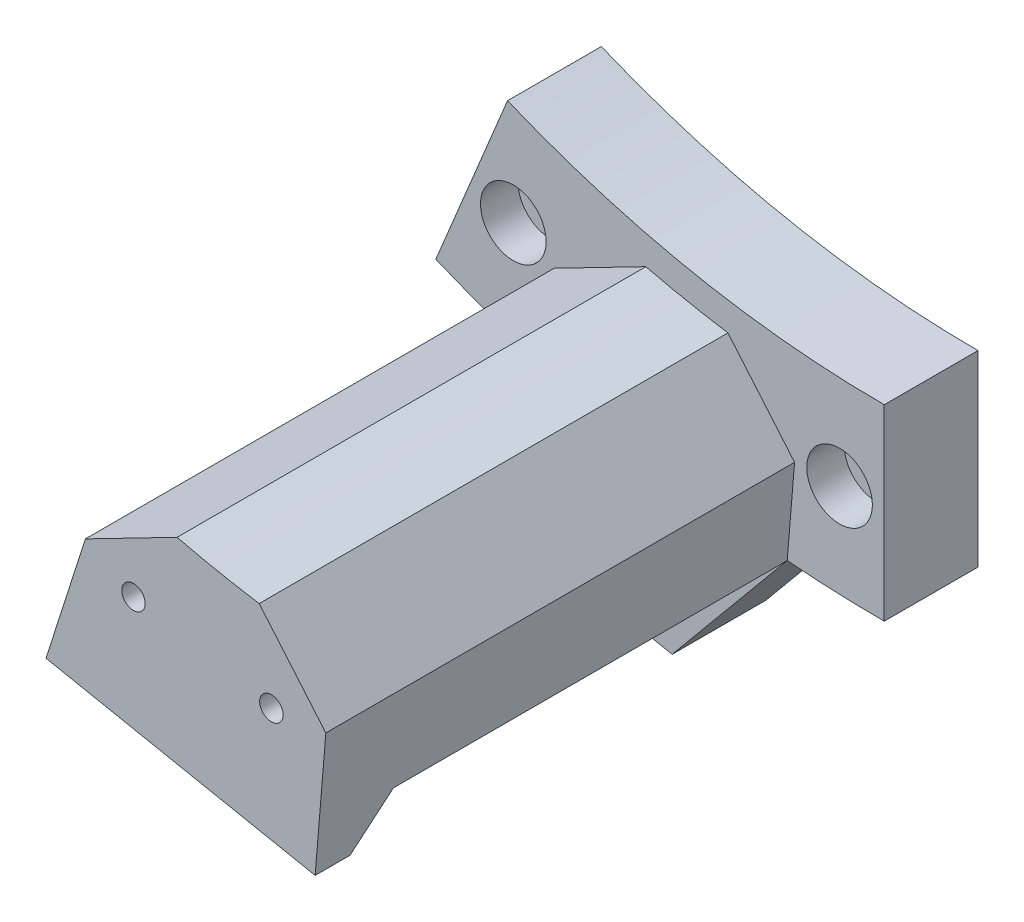
SolidWorks part; units mm, degrees
ref_plane "Plan de face" through (0, 0, 0) normal (0, 0, 1) x (1, 0, 0)
ref_plane "Plan de dessus" through (0, 0, 0) normal (0, 1, 0) x (1, 0, 0)
ref_plane "Plan de droite" through (0, 0, 0) normal (1, 0, 0) x (0, 0, -1)
sketch "Esquisse1" plane through (0, 0, 0) normal (0, 0, 1) x (1, 0, 0)
  line L0 (0, 0) -> (0, -125) construction
  line L1 (0, 0) -> (-47.8354, -115.4849) construction
  line L2 (-40.1818, -97.0074) -> (-47.8354, -115.4849)
  line L3 (0, -105) -> (0, -125)
  arc A0 (0, -125) -> (-47.8354, -115.4849) centre (0, 0) cw
  arc A1 (0, -105) -> (-40.1818, -97.0074) centre (0, 0) cw
  dimension "D2" = 125
  dimension "D3" = 105
  dimension "D1" = 22.5
extrude "Boss.-Extru.1" add sketch "Esquisse1" along normal blind 10
sketch "Esquisse2" plane through (0, 0, 10) normal (0, 0, 1) x (1, 0, 0)
  line L0 (0, 0) -> (-24.3863, -122.5982) construction
  line L1 (0, 0) -> (-10.351, -124.5707) construction
  line L2 (0, 0) -> (-38.108, -119.0495) construction
  line L3 (-32.9253, -102.8587) -> (-38.108, -119.0495)
  line L4 (-8.9433, -107.6291) -> (-10.351, -124.5707)
  arc A0 (-47.8354, -115.4849) -> (0, -125) centre (0, 0) ccw construction
  arc A1 (-10.351, -124.5707) -> (-38.108, -119.0495) centre (0, 0) cw
  arc A2 (-8.9433, -107.6291) -> (-32.9253, -102.8587) centre (0, 0) cw
  arc A3 (-40.1818, -97.0074) -> (0, -105) centre (0, 0) ccw construction
  point P10 (-24.3863, -122.5982)
  dimension "D1" = 3
  dimension "D2" = 13
extrude "Boss.-Extru.2" add sketch "Esquisse2" along normal blind 48
sketch "Esquisse4" plane through (0, 0, 58) normal (0, 0, 1) x (1, 0, 0)
  line L0 (-39.4132, -123.1267) -> (-10.7055, -128.837)
  line L1 (-10.7055, -128.837) -> (-8.9433, -107.6291)
  line L2 (-32.9253, -102.8587) -> (-39.4132, -123.1267)
  line L3 (-32.9253, -102.8587) -> (-38.108, -119.0495) construction
  line L4 (-10.351, -124.5707) -> (-8.9433, -107.6291) construction
  arc A0 (-32.9253, -102.8587) -> (-8.9433, -107.6291) centre (0, 0) ccw construction
  arc A1 (-32.9253, -102.8587) -> (-8.9433, -107.6291) centre (0, 0) ccw
  arc A2 (-38.108, -119.0495) -> (-10.351, -124.5707) centre (0, 0) ccw construction
  point P14 (-24.3863, -122.5982)
  dimension "D1" = 3.45
extrude "Boss.-Extru.3" add sketch "Esquisse4" along normal blind 2
chamfer "Chanfrein1" distance 6 angle 45 1 edges at (-24.3863, -122.5982, 58)
sketch "Esquisse5" plane through (0, 0, 10) normal (0, 0, 1) x (1, 0, 0)
  line L0 (0, 0) -> (-43.0087, -117.368) construction
  line L1 (0, 0) -> (-5.18, -124.8926) construction
  line L2 (-43.0087, -117.368) -> (-36.1273, -98.5891) construction
  line L3 (0, -125) -> (0, -105) construction
  line L4 (-40.1818, -97.0074) -> (-47.8354, -115.4849) construction
  arc A0 (-47.8354, -115.4849) -> (-38.108, -119.0495) centre (0, 0) ccw construction
  arc A1 (-10.351, -124.5707) -> (0, -125) centre (0, 0) ccw construction
  arc A2 (-40.1818, -97.0074) -> (0, -105) centre (0, 0) ccw construction
  arc A3 (0, -115) -> (-44.0086, -106.2461) centre (0, 0) cw construction
  circle A4 centre (-4.7656, -114.9012) radius 1.75
  circle A5 centre (-39.568, -107.9786) radius 1.75
  point P20 (-39.568, -107.9786)
  dimension "D1" = 3.5
extrude "Enlèv. mat.-Extru.1" cut sketch "Esquisse5" against normal up to next
sketch "Esquisse6" plane through (0, 0, 10) normal (0, 0, 1) x (1, 0, 0)
  circle A0 centre (-39.568, -107.9786) radius 3.5
  circle A1 centre (-4.7656, -114.9012) radius 3.5
  dimension "D1" = 7
extrude "Enlèv. mat.-Extru.2" cut sketch "Esquisse6" against normal blind 4
chamfer "Chanfrein2" distance 7.5 angle 45 2 edges at (-8.9433, -107.6291, 35) (-32.9253, -102.8587, 35)
sketch "Esquisse7" plane through (0, 0, 60) normal (0, 0, 1) x (1, 0, 0)
  line L0 (-21.0698, -105.9248) -> (-24.3863, -122.5982) construction
  line L1 (-30.0839, -112.7983) -> (-15.3721, -115.7247) construction
  arc A0 (-38.108, -119.0495) -> (-10.351, -124.5707) centre (0, 0) ccw construction
  arc A1 (-38.108, -119.0495) -> (-10.351, -124.5707) centre (0, 0) ccw construction
  arc A2 (-25.4295, -104.9635) -> (-16.674, -106.7051) centre (0, 0) ccw construction
  circle A3 centre (-30.0839, -112.7983) radius 1.25
  circle A4 centre (-15.3721, -115.7247) radius 1.25
  point P12 (-22.728, -114.2615)
  point P13 (-22.728, -114.2615)
  dimension "D1" = 2.5
  dimension "D2" = 15
extrude "Enlèv. mat.-Extru.3" cut sketch "Esquisse7" against normal blind 10
sketch "Esquisse8" plane through (0, 0, 0) normal (0, 0, -1) x (-1, 0, 0)
  line L0 (24.3863, -122.5982) -> (0, 0) construction
  line L2 (24.3863, -122.5982) -> (27.5468, -138.4869) construction
  line L3 (32.4334, -137.4246) -> (38.108, -119.0495)
  line L5 (32.4334, -137.4246) -> (22.6256, -139.3755)
  line L7 (22.6256, -139.3755) -> (10.351, -124.5707)
  line L8 (35.2118, -110.0017) -> (38.108, -119.0495) construction
  line L9 (35.2118, -110.0017) -> (38.108, -119.0495) construction
  arc A1 (38.108, -119.0495) -> (10.351, -124.5707) centre (0, 0) cw
  arc A5 (0, -125) -> (47.8354, -115.4849) centre (0, 0) ccw construction
  point P7 (0, 0)
  point P14 (0, 0)
  arc M14 (0, -125) -> (47.8354, -115.4849) centre (0, 0) ccw
  dimension "D2" = 141.2
  dimension "D3" = 10
extrude "Boss.-Extru.4" add sketch "Esquisse8" against normal blind 10 contours L7 L3 M14 region at (-25.6818, -129.111, 0)
sketch "Esquisse9" plane through (-27.5295, -138.4, 0) normal (-0.1951, -0.9808, 0) x (0.9808, -0.1951, 0)
  line L0 (5, 10) -> (-5, 0) construction
  circle A0 centre (0, 5) radius 2.75
  point P6 (0, 5)
  point P7 (0, 5)
  dimension "D1" = 5.5
extrude "Enlèv. mat.-Extru.4" cut sketch "Esquisse9" against normal blind 2
